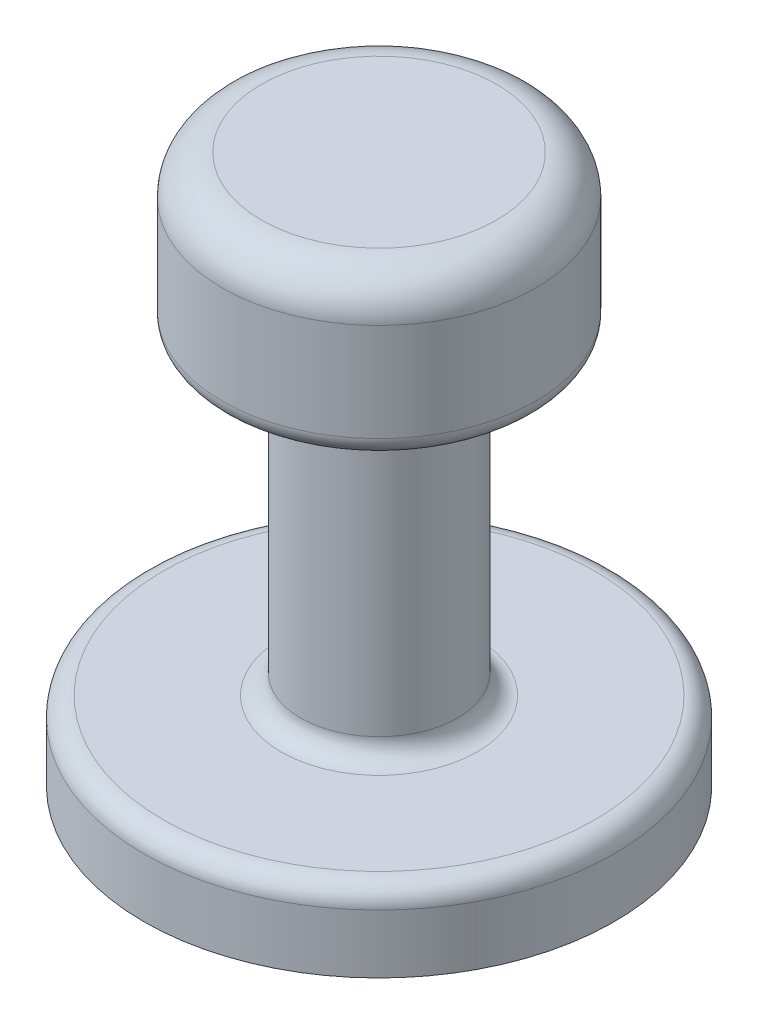
SolidWorks part; units mm, degrees
ref_plane "Front Plane" through (0, 0, 0) normal (0, 0, 1) x (1, 0, 0)
ref_plane "Top Plane" through (0, 0, 0) normal (0, 1, 0) x (1, 0, 0)
ref_plane "Right Plane" through (0, 0, 0) normal (1, 0, 0) x (0, 0, -1)
sketch "Sketch1" plane through (0, 0, 0) normal (0, 1, 0) x (1, 0, 0)
  circle A0 centre (0, 0) radius 3
  circle A1 centre (0, 0) radius 1
  circle A2 centre (0, 0) radius 2
  dimension "D1" = 6
  dimension "D2" = 2
  dimension "D3" = 4
extrude "Boss-Extrude1" add sketch "Sketch1" along normal blind 7 contours A2 A1 | A1 region at (0, 0, 0) region at (-1.9434, 0, 0)
extrude "Cut-Extrude2" cut sketch "Sketch1<5>" along normal blind 5 contours A2 A1 region at (-1.9434, 0, 0)
sketch "Sketch1<5>" plane through (0, 0, 0) normal (0, 1, 0) x (1, 0, 0) same geometry as "Sketch1"
extrude "Boss-Extrude3" add sketch "Sketch1<6>" along normal blind 1 contours A2 A1 | A0 A2 region at (-2.9151, 0, 0) region at (-1.9434, 0, 0)
sketch "Sketch1<6>" plane through (0, 0, 0) normal (0, 1, 0) x (1, 0, 0) same geometry as "Sketch1"
fillet "Fillet2" radius 0.5 1 edges at (0, 7, 2)
fillet "Fillet3" radius 0.25 1 edges at (0, 1, 3)
fillet "Fillet4" radius 0.25 2 edges at (0, 5, 2) (0, 5, 1)
fillet "Fillet5" radius 0.25 1 edges at (0, 1, 1)
